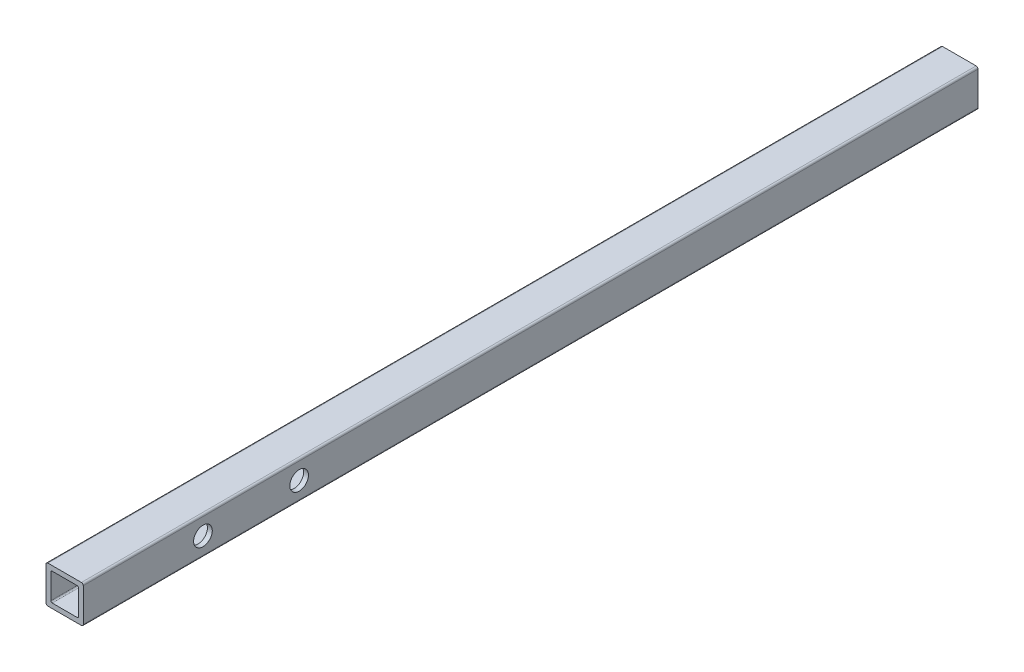
SolidWorks part; units mm, degrees
ref_plane "Front" through (0, 0, 0) normal (0, 0, 1) x (1, 0, 0)
ref_plane "Top" through (0, 0, 0) normal (0, 1, 0) x (1, 0, 0)
ref_plane "Right" through (0, 0, 0) normal (1, 0, 0) x (0, 0, -1)
sketch "Sketch1" plane through (0, 0, 0) normal (0, 0, 1) x (1, 0, 0)
  line L0 (-4.699, 0) -> (-6.35, 0) construction
  line L1 (5.715, -6.35) -> (-5.715, -6.35)
  line L2 (6.35, -5.715) -> (6.35, 5.715)
  line L3 (5.715, 6.35) -> (-5.715, 6.35)
  line L4 (-6.35, -5.715) -> (-6.35, 5.715)
  line L5 (6.35, -6.35) -> (-6.35, 6.35) construction
  line L6 (6.35, 6.35) -> (-6.35, -6.35) construction
  line L7 (4.2291, 4.699) -> (-4.2291, 4.699)
  line L8 (4.699, 4.2291) -> (4.699, -4.2291)
  line L9 (4.2291, -4.699) -> (-4.2291, -4.699)
  line L10 (-4.699, 4.2291) -> (-4.699, -4.2291)
  line L11 (4.699, 4.699) -> (-4.699, -4.699) construction
  line L12 (4.699, -4.699) -> (-4.699, 4.699) construction
  line L13 (0, -4.699) -> (0, -6.35) construction
  line L14 (4.699, -4.2291) -> (4.699, -6.35) construction
  line L15 (4.699, 0) -> (6.35, 0) construction
  line L16 (4.699, -6.35) -> (6.35, -6.35) construction
  arc A0 (-4.2291, -4.699) -> (-4.699, -4.2291) centre (-4.2291, -4.2291) cw
  arc A1 (4.699, -4.2291) -> (4.2291, -4.699) centre (4.2291, -4.2291) cw
  arc A2 (4.2291, 4.699) -> (4.699, 4.2291) centre (4.2291, 4.2291) cw
  arc A3 (-4.2291, 4.699) -> (-4.699, 4.2291) centre (-4.2291, 4.2291) ccw
  arc A4 (5.715, -6.35) -> (6.35, -5.715) centre (5.715, -5.715) ccw
  arc A5 (6.35, 5.715) -> (5.715, 6.35) centre (5.715, 5.715) ccw
  arc A6 (-5.715, 6.35) -> (-6.35, 5.715) centre (-5.715, 5.715) ccw
  arc A7 (-5.715, -6.35) -> (-6.35, -5.715) centre (-5.715, -5.715) cw
  point P0 (0, 0)
  point P6 (0, 0)
  dimension "D2" = 0.4699
  dimension "D3" = 0.635
  dimension "Outside Width" = 12.7
  dimension "Ouside Height" = 12.7
  dimension "Wall Thickness" = 1.651
sketch "Sketch2" plane through (0, 0, 0) normal (1, 0, 0) x (0, 0, -1)
  line L0 (-152.4, 0) -> (152.4, 0) construction
  dimension "Length" = 304.8
ref_plane "Plane1" through (6.35, 0, 0) normal (1, 0, 0) x (0, 0, -1)
sketch "Sketch5" plane through (6.35, 0, 0) normal (1, 0, 0) x (0, 0, -1)
  line L0 (-152.4, 6.35) -> (-152.4, -6.35) construction
  line L1 (152.4, 6.35) -> (152.4, -6.35) construction
sketch "Sketch4" plane through (0, 0, 0) normal (0, 0, 1) x (1, 0, 0)
  line L0 (6.35, -5.715) -> (6.35, 5.715) construction
  line L1 (5.715, 6.35) -> (-5.715, 6.35) construction
  line L2 (-6.35, -5.715) -> (-6.35, 5.715) construction
  line L3 (5.715, -6.35) -> (-5.715, -6.35) construction
  line L4 (4.699, 4.2291) -> (4.699, -4.2291) construction
  line L5 (4.2291, -4.699) -> (-4.2291, -4.699) construction
  line L6 (-4.699, 4.2291) -> (-4.699, -4.2291) construction
  line L7 (4.2291, 4.699) -> (-4.2291, 4.699) construction
  line L8 (6.35, -5.715) -> (6.35, 5.715)
  line L9 (5.715, 6.35) -> (-5.715, 6.35)
  line L10 (-6.35, -5.715) -> (-6.35, 5.715)
  line L11 (5.715, -6.35) -> (-5.715, -6.35)
  line L12 (4.699, 4.2291) -> (4.699, -4.2291)
  line L13 (4.2291, -4.699) -> (-4.2291, -4.699)
  line L14 (-4.699, 4.2291) -> (-4.699, -4.2291)
  line L15 (4.2291, 4.699) -> (-4.2291, 4.699)
  arc A0 (6.35, 5.715) -> (5.715, 6.35) centre (5.715, 5.715) ccw construction
  arc A1 (-5.715, 6.35) -> (-6.35, 5.715) centre (-5.715, 5.715) ccw construction
  arc A2 (-6.35, -5.715) -> (-5.715, -6.35) centre (-5.715, -5.715) ccw construction
  arc A3 (5.715, -6.35) -> (6.35, -5.715) centre (5.715, -5.715) ccw construction
  arc A4 (4.2291, -4.699) -> (4.699, -4.2291) centre (4.2291, -4.2291) ccw construction
  arc A5 (-4.699, -4.2291) -> (-4.2291, -4.699) centre (-4.2291, -4.2291) ccw construction
  arc A6 (-4.2291, 4.699) -> (-4.699, 4.2291) centre (-4.2291, 4.2291) ccw construction
  arc A7 (4.699, 4.2291) -> (4.2291, 4.699) centre (4.2291, 4.2291) ccw construction
  arc A8 (6.35, 5.715) -> (5.715, 6.35) centre (5.715, 5.715) ccw
  arc A9 (-5.715, 6.35) -> (-6.35, 5.715) centre (-5.715, 5.715) ccw
  arc A10 (-6.35, -5.715) -> (-5.715, -6.35) centre (-5.715, -5.715) ccw
  arc A11 (5.715, -6.35) -> (6.35, -5.715) centre (5.715, -5.715) ccw
  arc A12 (4.2291, -4.699) -> (4.699, -4.2291) centre (4.2291, -4.2291) ccw
  arc A13 (-4.699, -4.2291) -> (-4.2291, -4.699) centre (-4.2291, -4.2291) ccw
  arc A14 (-4.2291, 4.699) -> (-4.699, 4.2291) centre (-4.2291, 4.2291) ccw
  arc A15 (4.699, 4.2291) -> (4.2291, 4.699) centre (4.2291, 4.2291) ccw
extrude "Boss-Extrude1" add sketch "Sketch4" along normal up to vertex (152.4 mm away) and the other way up to vertex (152.4 mm away) up to point (0, 0, 152.4) other way up to point (0, 0, -152.4)
hole_wizard "1/4 (0.25) Diameter Hole1" positions "Sketch6" profile "Sketch7" hole size "1/4" standard "ANSI Inch" end condition through all
sketch "Sketch6" plane through (-6.35, 0, 0) normal (-1, 0, 0) x (0, 0, 1)
  point P0 (78.868, 0)
  point P2 (111.632, 0)
sketch "Sketch7" plane through (-6.35, 0, 78.868) normal (0, 1, 0) x (0, 0, 1)
  line L0 (0, 0) -> (0, 12.7)
  line L1 (0, 12.7) -> (3.175, 12.7)
  line L2 (3.175, 12.7) -> (3.175, 0)
  line L5 (3.175, 0) -> (0, 0)
  line L11 (0, -6.35) -> (0, 107.95) construction
  dimension "Thru Hole Dia." = 6.35
  dimension "Thru Hole Depth" = 12.7
equation "\"D3@Sketch1\"=\"Outside Width@Sketch1\"*.05"
equation "\"D2@Sketch1\"=\"D1@Sketch1\"*.05"
